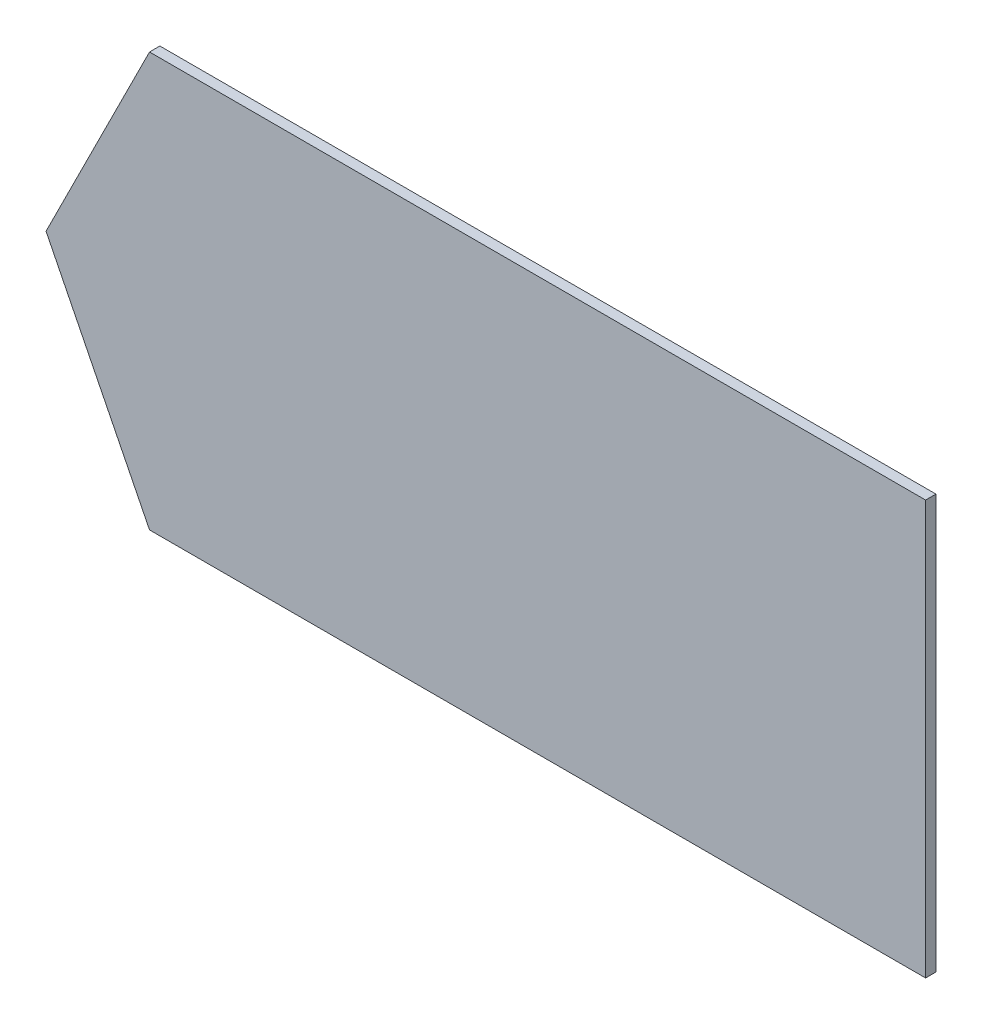
SolidWorks part; units mm, degrees
ref_plane "前视基准面" through (0, 0, 0) normal (0, 0, 1) x (1, 0, 0)
ref_plane "上视基准面" through (0, 0, 0) normal (0, 1, 0) x (1, 0, 0)
ref_plane "右视基准面" through (0, 0, 0) normal (1, 0, 0) x (0, 0, -1)
sketch "草图2" plane through (0, 0, 0) normal (0, 0, 1) x (1, 0, 0)
  line L0 (-1003.8117, 0) -> (49186.7727, 0) construction
  line L1 (0, -1003.8117) -> (0, 49186.7727) construction
  line L2 (-75, 40) -> (75, 40)
  line L3 (75, 40) -> (75, -40)
  line L5 (-75, -40) -> (75, -40)
  line L7 (-95, 0) -> (-75, 40)
  line L8 (-95, 0) -> (-75, -40)
  point P12 (75, 0)
  dimension "D1" = 150
  dimension "D2" = 80
  dimension "D3" = 40
  dimension "D4" = 75
  dimension "D5" = 170
extrude "凸台-拉伸2" add sketch "草图2" along normal mid plane 2 contours L7 L2 L3 L5 L8
